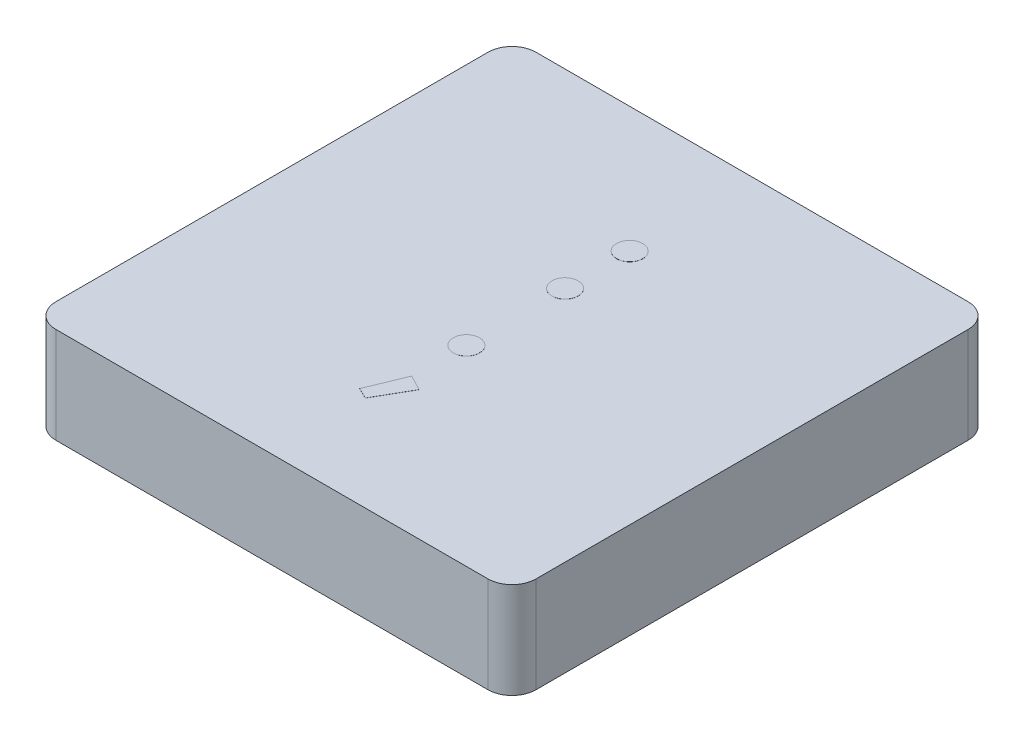
SolidWorks part; units mm, degrees
ref_plane "Front Plane" through (0, 0, 0) normal (0, 0, 1) x (1, 0, 0)
ref_plane "Top Plane" through (0, 0, 0) normal (0, 1, 0) x (1, 0, 0)
ref_plane "Right Plane" through (0, 0, 0) normal (1, 0, 0) x (0, 0, -1)
sketch "Sketch1" plane through (0, 0, 0) normal (0, 1, 0) x (1, 0, 0)
  line L0 (0, 0) -> (12.7, 0)
  line L1 (12.7, 0) -> (12.7, 12.7)
  line L2 (12.7, 12.7) -> (0, 12.7)
  line L3 (0, 12.7) -> (0, 0)
  dimension "D1" = 12.7
  dimension "D2" = 12.7
extrude "Boss-Extrude1" add sketch "Sketch1" along normal blind 2.54
fillet "Fillet1" radius 0.635 4 edges at (0, 1.27, -12.7) (12.7, 1.27, -12.7) (12.7, 1.27, 0) (0, 1.27, 0)
shell "Shell1" thickness 0.635 removed face at (6.35, 0, -6.35)
sketch "Sketch2" plane through (0, 1.905, 0) normal (0, -1, 0) x (-1, 0, 0)
  line L0 (-0.635, 6.35) -> (-12.065, 6.35) construction
  line L1 (-0.635, 12.065) -> (-0.635, 0.635) construction
  line L2 (-12.065, 0.635) -> (-12.065, 12.065) construction
  line L3 (-6.35, 0.635) -> (-6.35, 12.065) construction
  line L4 (-0.635, 0.635) -> (-12.065, 0.635) construction
  line L5 (-12.065, 12.065) -> (-0.635, 12.065) construction
  circle A0 centre (-6.35, 6.35) radius 2.54
  dimension "D1" = 5.08
extrude "Boss-Extrude2" add sketch "Sketch2" along normal up to surface (1.905 mm away) up to face at (6.35, 0, -6.35)
sketch "Sketch3" plane through (0, 2.54, 0) normal (0, 1, 0) x (1, 0, 0)
  line L0 (0.635, 0) -> (12.065, 0) construction
  line L1 (0, 12.065) -> (0, 0.635) construction
  line L2 (12.065, 12.7) -> (0.635, 12.7) construction
  text T0 "<b>:</b>"
  text T1 "<b>;</b>"
  dimension "D1" = 3.048
  dimension "D2" = 5.842
  dimension "D3" = 5.334
  dimension "D4" = 5.842
extrude "Boss-Extrude3" add sketch "Sketch3" along normal blind 0.0025
